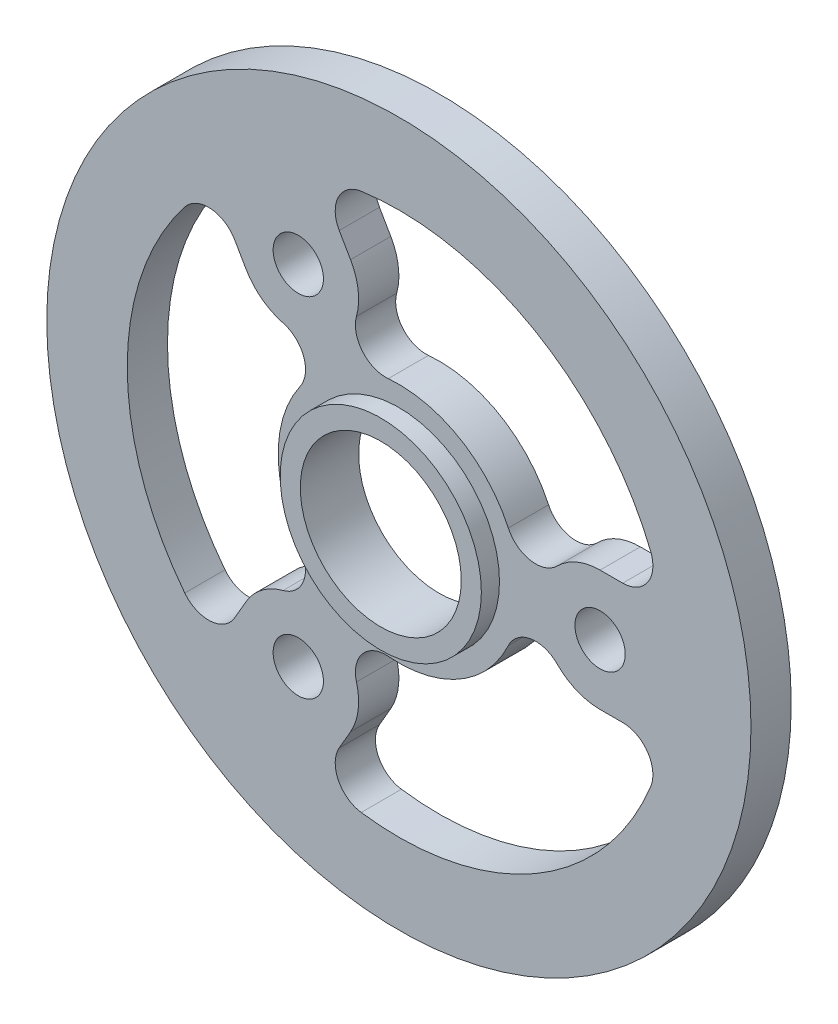
SolidWorks part; units mm, degrees
material "A2017"
ref_plane "正面" through (0, 0, 0) normal (0, 0, 1) x (1, 0, 0)
ref_plane "平面" through (0, 0, 0) normal (0, 1, 0) x (1, 0, 0)
ref_plane "右側面" through (0, 0, 0) normal (1, 0, 0) x (0, 0, -1)
sketch "ｽｹｯﾁ1" plane through (0, 0, 0) normal (1, 0, 0) x (0, 0, -1)
  line L0 (0, 0) -> (5.1985, 0) construction
  line L1 (0, 4) -> (2.9, 4)
  line L2 (2.9, 4) -> (2.9, 17.5)
  line L3 (2.9, 17.5) -> (0.9, 17.5)
  line L4 (0.9, 17.5) -> (0.9, 5)
  line L5 (0.9, 5) -> (0, 5)
  line L6 (0, 5) -> (0, 4)
  dimension "D1" = 35
  dimension "D2" = 2.9
  dimension "D3" = 2
  dimension "D4" = 10
  dimension "D5" = 8
revolve "回転1" add sketch "ｽｹｯﾁ1" angle 360 about L0
hole_wizard "M3 ねじ穴1" positions "ｽｹｯﾁ2" profile "ｽｹｯﾁ3" tap size "M3" standard "JIS" end condition through all
sketch "ｽｹｯﾁ2" plane through (0, 0, -0.9) normal (0, 0, 1) x (1, 0, 0)
  point P0 (10, 0)
  point P3 (-5, 8.6603)
  point P6 (-5, -8.6603)
sketch "ｽｹｯﾁ3" plane through (10, 0, -0.9) normal (1, 0, 0) x (0, -1, 0)
  line L0 (0, 0) -> (0, 2)
  line L1 (0, 2) -> (1.25, 2)
  line L2 (1.25, 2) -> (1.25, 0)
  line L5 (1.25, 0) -> (0, 0)
  line L11 (0, -6.35) -> (0, 107.95) construction
  dimension "次ｻｰﾌｪｽまでのねじ下穴ﾄﾞﾘﾙ直径" = 2.5
  dimension "次ｻｰﾌｪｽまでのねじ下穴ﾄﾞﾘﾙの深さ" = 2
cosmetic thread "穴のねじ山1" parameters "D2"=3
cosmetic thread "穴のねじ山2" parameters "D2"=3
cosmetic thread "穴のねじ山3" parameters "D2"=3
sketch "ｽｹｯﾁ4" plane through (0, 0, -0.9) normal (0, 0, 1) x (1, 0, 0)
  line L0 (10, 0) -> (13.5, 0) construction
  line L1 (10, 3) -> (13.5, 3)
  line L2 (10, -3) -> (13.5, -3)
  line L3 (-5, -8.6603) -> (-6.75, -11.6913) construction
  line L4 (-2.4019, -10.1603) -> (-4.1519, -13.1913)
  line L5 (-7.5981, -7.1603) -> (-9.3481, -10.1913)
  line L6 (-5, 8.6603) -> (-6.75, 11.6913) construction
  line L7 (-7.5981, 7.1603) -> (-9.3481, 10.1913)
  line L8 (-2.4019, 10.1603) -> (-4.1519, 13.1913)
  line L9 (0, 0) -> (10, 0) construction
  circle A0 centre (0, 0) radius 13.5
  arc A1 (10, 3) -> (10, -3) centre (10, 0) ccw
  arc A2 (13.5, -3) -> (13.5, 3) centre (13.5, 0) ccw
  arc A3 (-2.4019, -10.1603) -> (-7.5981, -7.1603) centre (-5, -8.6603) ccw
  arc A4 (-9.3481, -10.1913) -> (-4.1519, -13.1913) centre (-6.75, -11.6913) ccw
  arc A5 (-7.5981, 7.1603) -> (-2.4019, 10.1603) centre (-5, 8.6603) ccw
  arc A6 (-4.1519, 13.1913) -> (-9.3481, 10.1913) centre (-6.75, 11.6913) ccw
  circle A7 centre (0, 0) radius 6
  arc A8 (5.44, 2.5311) -> (7.8667, 2.1092) centre (6.8, 3.1639) ccw
  arc A9 (5.44, -2.5311) -> (7.8667, -2.1092) centre (6.8, -3.1639) cw
  arc A10 (-4.912, -3.4456) -> (-5.76, -5.7581) centre (-6.14, -4.307) cw
  arc A11 (-0.528, -5.9767) -> (-2.1067, -7.8674) centre (-0.66, -7.4709) ccw
  arc A12 (-0.528, 5.9767) -> (-2.1067, 7.8674) centre (-0.66, 7.4709) cw
  arc A13 (-4.912, 3.4456) -> (-5.76, 5.7581) centre (-6.14, 4.307) ccw
  point P6 (11.75, 0)
  point P15 (-5.875, -10.1758)
  point P22 (-5.875, 10.1758)
  point P34 (0, 0)
  point P49 (0, 0)
  dimension "D1" = 27
  dimension "D4" = 12
  dimension "D5" = 3
  dimension "D2" = 6
  dimension "D3" = 3
  dimension "D6" = 3
extrude "ｶｯﾄ - 押し出し1" cut sketch "ｽｹｯﾁ4" against normal through all contours A7 A13 A5 L7 A0 L5 A3 A10 | A12 A7 A8 A1 L1 A0 L8 A5 | A7 A11 A3 L4 A0 L2 A1 A9 region at (4.6223, 8.0061, -0.9) region at (4.6223, -8.0061, -0.9) region at (-9.2446, 0, -0.9)
fillet "ﾌｨﾚｯﾄ1" radius 1.5 6 edges at (13.1624, 3, -1.9) (-9.1793, -9.899, -1.9) (13.1624, -3, -1.9) (-3.9831, -12.899, -1.9) (-9.1793, 9.899, -1.9) (-3.9831, 12.899, -1.9)
sketch "歯車作図" [suppressed] plane through (0, 0, -0.9) normal (0, 0, 1) x (1, 0, 0)
  line L0 (0, 0) -> (25.5, 0) construction
  line L1 (25.5, 0) -> (26.3114, 0)
  line L2 (0, 0) -> (29.9745, -1.2355)
  circle A0 centre (0, 0) radius 30
  circle A1 centre (0, 0) radius 28 construction
  circle A2 centre (0, 0) radius 26.3114 construction
  circle A3 centre (0, 0) radius 25.5 construction
  arc A4 (27.9762, -1.1531) -> (27.9969, 0.4173) centre (0, 0) ccw
  spline S0 degree 4 poles (26.3114, 0) (26.3519, 0.0013) (26.4329, 0.0063) (26.6589, 0.033) (27.0848, 0.1166) (27.7247, 0.3006) (28.5755, 0.6367) (29.6254, 1.1673) (30.7905, 1.9033) (31.9912, 2.8259) (33.1927, 3.9303) (34.3032, 5.1257) (35.3247, 6.3978) (36.3053, 7.8011) (37.4014, 9.6156) (38.528, 11.8801) (39.5864, 14.6214) (40.4562, 17.7686) (41.0337, 20.9817) (41.3324, 24.232) (41.3656, 27.4956) (41.1738, 30.3444) (40.8594, 32.7708) (40.5015, 34.7769) (40.1586, 36.3716) (39.762, 37.9517) (39.3106, 39.5208) (38.8102, 41.0681) (38.3238, 42.4169) (37.8838, 43.5452) (37.5131, 44.4365) (37.2634, 45.0171) (36.9734, 45.666) (36.7803, 46.0867) (36.463, 46.7613) (36.2065, 47.2825) (35.8912, 47.9127) (35.6004, 48.4699) (35.2823, 49.0677) (34.9714, 49.6307) (34.7238, 50.0704) (34.5624, 50.3492) (34.4786, 50.4938) knots 0 0 0 0 0 0.002802 0.005604 0.015718 0.02996 0.048734 0.068727 0.096889 0.125051 0.153212 0.181374 0.209535 0.237696 0.271429 0.327752 0.384075 0.440398 0.496721 0.553044 0.609367 0.66569 0.693852 0.722013 0.750174 0.778336 0.806497 0.834659 0.86282 0.876901 0.890982 0.900036 0.909091 0.920455 0.931818 0.943182 0.954545 0.965909 0.977273 0.988636 1 1 1 1 1 construction
  spline S1 degree 4 poles (26.3114, 0) (26.3519, 0.0013) (26.4329, 0.0063) (26.6589, 0.033) (27.0848, 0.1166) (27.7247, 0.3006) (28.5755, 0.6367) (29.6254, 1.1673) (30.7905, 1.9033) (31.9912, 2.8259) (33.1927, 3.9303) (34.3032, 5.1257) (35.3247, 6.3978) (36.3053, 7.8011) (37.4014, 9.6156) (38.528, 11.8801) (39.5864, 14.6214) (40.4562, 17.7686) (41.0337, 20.9817) (41.3324, 24.232) (41.3656, 27.4956) (41.1738, 30.3444) (40.8594, 32.7708) (40.5015, 34.7769) (40.1586, 36.3716) (39.762, 37.9517) (39.3106, 39.5208) (38.8102, 41.0681) (38.3238, 42.4169) (37.8838, 43.5452) (37.5131, 44.4365) (37.2634, 45.0171) (37.049, 45.4967) (36.9499, 45.7154) (36.9004, 45.8237) knots 0 0 0 0 0 0.002802 0.005604 0.015718 0.02996 0.048734 0.068727 0.096889 0.125051 0.153212 0.181374 0.209535 0.237696 0.271429 0.327752 0.384075 0.440398 0.496721 0.553044 0.609367 0.66569 0.693852 0.722013 0.750174 0.778336 0.806497 0.834659 0.86282 0.876901 0.890982 0.900036 0.909091 0.909091 0.909091 0.909091 0.909091
  dimension "歯先円直径" = 60
  dimension "基礎ピッチ円直径" = 56
  dimension "基礎円直径" = 52.6228
  dimension "全歯丈" = 4.5
  dimension "基準ピッチ" = 1.5708
sketch "ｽｹｯﾁ6" [suppressed] plane through (0, 0, -0.9) normal (0, 0, 1) x (1, 0, 0)
  circle A0 centre (0, 0) radius 30 construction
  circle A1 centre (0, 0) radius 30
  circle A3 centre (0, 0) radius 17.5
  circle A4 centre (0, 0) radius 17.5
  dimension "D1" = 0
extrude "ﾎﾞｽ - 押し出し1" [suppressed] add sketch "ｽｹｯﾁ6" against normal through all
sketch "ｽｹｯﾁ7" [suppressed] plane through (0, 0, -0.9) normal (0, 0, 1) x (1, 0, 0)
  line L0 (25.5, 0) -> (26.3114, 0) construction
  line L1 (0, 0) -> (29.9745, -1.2355) construction
  line L2 (25.5, 0) -> (26.3114, 0)
  line L3 (25.4784, -1.0502) -> (29.9745, -1.2355)
  circle A1 centre (0, 0) radius 30
  arc A2 (29.9745, -1.2355) -> (29.9674, 1.3986) centre (0, 0) ccw
  circle A3 centre (0, 0) radius 25.5 construction
  arc A4 (25.4784, -1.0502) -> (25.5, 0) centre (0, 0) ccw
  spline S0 degree 4 poles (18.0064, -999.7701) (20.0439, 38.1516) (22.4374, 0.7712) (24.776, -0.3364) (27.0848, 0.1166) (27.7247, 0.3006) (28.5755, 0.6367) (29.6254, 1.1673) (30.7905, 1.9033) (31.9912, 2.8259) (33.1927, 3.9303) (34.3032, 5.1257) (35.3247, 6.3978) (36.3053, 7.8011) (37.4014, 9.6156) (38.528, 11.8801) (39.5864, 14.6214) (40.4562, 17.7686) (41.0337, 20.9817) (41.3324, 24.232) (41.3656, 27.4956) (41.1738, 30.3444) (40.8594, 32.7708) (40.5015, 34.7769) (40.1586, 36.3716) (39.762, 37.9517) (39.3106, 39.5208) (38.8102, 41.0681) (38.3238, 42.4169) (37.8838, 43.5452) (37.5131, 44.4365) (36.5867, 46.5912) (34.7604, 50.3825) (49.4042, 17.9493) (-379.6911, 954.9172) knots -0.132452 -0.132452 -0.132452 -0.132452 -0.132452 0.002802 0.005604 0.015718 0.02996 0.048734 0.068727 0.096889 0.125051 0.153212 0.181374 0.209535 0.237696 0.271429 0.327752 0.384075 0.440398 0.496721 0.553044 0.609367 0.66569 0.693852 0.722013 0.750174 0.778336 0.806497 0.834659 0.86282 0.876901 0.890982 0.900036 1.034522 1.034522 1.034522 1.034522 1.034522 only from (26.3114, 0) to (36.9004, 45.8237) construction
  spline S1 degree 4 poles (26.3114, 0) (26.3519, 0.0013) (26.4329, 0.0063) (26.6589, 0.033) (27.0848, 0.1166) (27.7247, 0.3006) (28.5683, 0.6339) (29.2472, 0.9762) (29.727, 1.252) (29.9674, 1.3986) knots 0 0 0 0 0 0.002802 0.005604 0.015718 0.02996 0.048734 0.06819 0.06819 0.06819 0.06819 0.06819
  dimension "D1" = 0
extrude "ｶｯﾄ - 押し出し2" [suppressed] cut sketch "ｽｹｯﾁ7" against normal through all
pattern_circular "円形ﾊﾟﾀｰﾝ1" [suppressed] count 28 over 360 of bodies 106
mirror "ﾐﾗｰ1" [suppressed]
sketch "ｽｹｯﾁ8" [suppressed] plane through (0, 0, -0.9) normal (0, 0, 1) x (1, 0, 0)
  circle A0 centre (1.0502, 25.4784) radius 1.0504
  arc A1 (2.0986, 25.4135) -> (0, 25.5) centre (0, 0) ccw construction
extrude "ｶｯﾄ - 押し出し3" [suppressed] cut sketch "ｽｹｯﾁ8" against normal through all
pattern_circular "円形ﾊﾟﾀｰﾝ2" [suppressed] count 28 over 360 of bodies 109
sketch "ｽｹｯﾁ9" [suppressed] plane through (0, 0, -0.9) normal (0, 0, 1) x (1, 0, 0)
  line L0 (0, 0) -> (19, 0) construction
  line L1 (0, 0) -> (18.3526, -4.9176) construction
  line L2 (18.3526, 4.9176) -> (0, 0) construction
  circle A0 centre (0, 0) radius 16 construction
  circle A1 centre (0, 0) radius 22 construction
  arc A2 (18.3526, -4.9176) -> (18.3526, 4.9176) centre (0, 0) ccw construction
  arc A3 (21.2504, -5.694) -> (21.2504, 5.694) centre (0, 0) ccw
  arc A4 (15.4548, -4.1411) -> (15.4548, 4.1411) centre (0, 0) ccw
  arc A5 (15.4548, -4.1411) -> (21.2504, -5.694) centre (18.3526, -4.9176) ccw
  arc A6 (21.2504, 5.694) -> (15.4548, 4.1411) centre (18.3526, 4.9176) ccw
  arc A7 (4.9176, -18.3526) -> (13.435, -13.435) centre (0, 0) ccw construction
  arc A8 (5.694, -21.2504) -> (15.5563, -15.5563) centre (0, 0) ccw
  arc A9 (4.1411, -15.4548) -> (11.3137, -11.3137) centre (0, 0) ccw
  arc A10 (4.1411, -15.4548) -> (5.694, -21.2504) centre (4.9176, -18.3526) ccw
  arc A11 (15.5563, -15.5563) -> (11.3137, -11.3137) centre (13.435, -13.435) ccw
  arc A12 (-13.435, -13.435) -> (-4.9176, -18.3526) centre (0, 0) ccw construction
  arc A13 (-15.5563, -15.5563) -> (-5.694, -21.2504) centre (0, 0) ccw
  arc A14 (-11.3137, -11.3137) -> (-4.1411, -15.4548) centre (0, 0) ccw
  arc A15 (-11.3137, -11.3137) -> (-15.5563, -15.5563) centre (-13.435, -13.435) ccw
  arc A16 (-5.694, -21.2504) -> (-4.1411, -15.4548) centre (-4.9176, -18.3526) ccw
  arc A17 (-18.3526, 4.9176) -> (-18.3526, -4.9176) centre (0, 0) ccw construction
  arc A18 (-21.2504, 5.694) -> (-21.2504, -5.694) centre (0, 0) ccw
  arc A19 (-15.4548, 4.1411) -> (-15.4548, -4.1411) centre (0, 0) ccw
  arc A20 (-15.4548, 4.1411) -> (-21.2504, 5.694) centre (-18.3526, 4.9176) ccw
  arc A21 (-21.2504, -5.694) -> (-15.4548, -4.1411) centre (-18.3526, -4.9176) ccw
  arc A22 (-4.9176, 18.3526) -> (-13.435, 13.435) centre (0, 0) ccw construction
  arc A23 (-5.694, 21.2504) -> (-15.5563, 15.5563) centre (0, 0) ccw
  arc A24 (-4.1411, 15.4548) -> (-11.3137, 11.3137) centre (0, 0) ccw
  arc A25 (-4.1411, 15.4548) -> (-5.694, 21.2504) centre (-4.9176, 18.3526) ccw
  arc A26 (-15.5563, 15.5563) -> (-11.3137, 11.3137) centre (-13.435, 13.435) ccw
  arc A27 (13.435, 13.435) -> (4.9176, 18.3526) centre (0, 0) ccw construction
  arc A28 (15.5563, 15.5563) -> (5.694, 21.2504) centre (0, 0) ccw
  arc A29 (11.3137, 11.3137) -> (4.1411, 15.4548) centre (0, 0) ccw
  arc A30 (11.3137, 11.3137) -> (15.5563, 15.5563) centre (13.435, 13.435) ccw
  arc A31 (5.694, 21.2504) -> (4.1411, 15.4548) centre (4.9176, 18.3526) ccw
  point P6 (19, 0)
  point P20 (9.5, -16.4545)
  point P27 (-9.5, -16.4545)
  point P34 (-19, 0)
  point P41 (-9.5, 16.4545)
  point P48 (9.5, 16.4545)
  point P53 (0, 0)
  dimension "D1" = 32
  dimension "D2" = 44
  dimension "D3" = 6
  dimension "D4" = 30
  dimension "D5" = 6
extrude "ｶｯﾄ - 押し出し4" [suppressed] cut sketch "ｽｹｯﾁ9" against normal through all
equation "\"モジュール\"= 2"
equation "\"歯数\"= 28"
equation "\"圧力角\"= 20"
equation "\"歯先円直径@歯車作図\" =  ( \"歯数\" + 2 )  * \"モジュール\""
equation "\"基礎ピッチ円直径@歯車作図\" = \"モジュール\" * \"歯数\""
equation "\"基礎円直径@歯車作図\" = \"歯数\" * \"モジュール\" * cos ( \"圧力角\" ) "
equation "\"全歯丈@歯車作図\" = 2.25 * \"モジュール\""
equation "\"基準ピッチ@歯車作図\" = PI * \"モジュール\" / 4"
equation "\"D1@円形ﾊﾟﾀｰﾝ1\"=\"歯数\""
equation "\"D1@円形ﾊﾟﾀｰﾝ2\"=\"歯数\""
